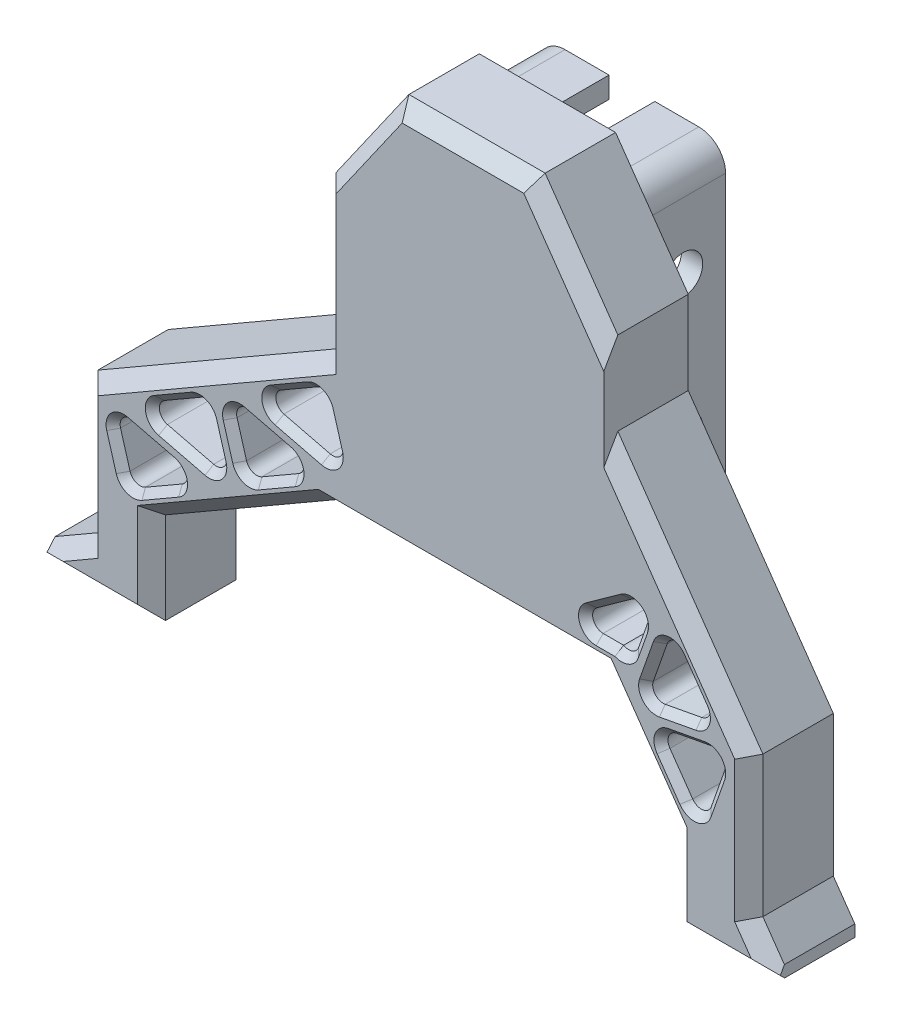
SolidWorks part; units mm, degrees
ref_plane "Front Plane" through (0, 0, 0) normal (0, 0, 1) x (1, 0, 0)
ref_plane "Top Plane" through (0, 0, 0) normal (0, 1, 0) x (1, 0, 0)
ref_plane "Right Plane" through (0, 0, 0) normal (1, 0, 0) x (0, 0, -1)
sketch "Sketch1" plane through (0, 0, 0) normal (0, 0, 1) x (1, 0, 0)
  line L0 (-3.25, 20.3) -> (-3.25, 23.3)
  line L1 (-3.05, 20.9) -> (-3.05, 23.3537) construction
  line L2 (3.25, 23.3) -> (3.25, 20.3)
  line L3 (3.05, 20.9) -> (3.05, 23.3537) construction
  line L94 (-10, -14.58) -> (-10, -19.5)
  line L95 (-9.5, -20) -> (-4.58, -20)
  line L96 (-4.58, -20) -> (-3.125, -18.545)
  line L97 (-3.125, -18.545) -> (-3.125, -18.2)
  line L98 (-3.125, -18.2) -> (-5.5, -18.2)
  line L99 (-5.5, -18.2) -> (-5.5, -16.5607)
  line L100 (-5.5, -16.5607) -> (-2.8393, -13.9)
  line L101 (-2.8393, -13.9) -> (-0.2, -13.9)
  line L102 (-0.2, -13.9) -> (0, -13.7)
  line L103 (0, -13.7) -> (0.2, -13.9)
  line L104 (0.2, -13.9) -> (2.8393, -13.9)
  line L105 (2.8393, -13.9) -> (5.5, -16.5607)
  line L106 (5.5, -16.5607) -> (5.5, -18.2)
  line L107 (5.5, -18.2) -> (3.125, -18.2)
  line L108 (3.125, -18.2) -> (3.125, -18.545)
  line L109 (3.125, -18.545) -> (4.58, -20)
  line L110 (4.58, -20) -> (9.5, -20)
  line L111 (10, -19.5) -> (10, -14.58)
  line L112 (10, -14.58) -> (8.545, -13.125)
  line L113 (8.545, -13.125) -> (8.2, -13.125)
  line L114 (8.2, -13.125) -> (8.2, -15.5)
  line L115 (8.2, -15.5) -> (6.5607, -15.5)
  line L116 (6.5607, -15.5) -> (3.9, -12.8393)
  line L117 (3.9, -12.8393) -> (3.9, -10.2)
  line L118 (3.9, -10.2) -> (3.7, -10)
  line L119 (3.7, -10) -> (3.9, -9.8)
  line L120 (3.9, -9.8) -> (3.9, -7.1607)
  line L121 (3.9, -7.1607) -> (6.5607, -4.5)
  line L122 (6.5607, -4.5) -> (8.2, -4.5)
  line L123 (8.2, -4.5) -> (8.2, -6.875)
  line L124 (8.2, -6.875) -> (8.545, -6.875)
  line L125 (8.545, -6.875) -> (10, -5.42)
  line L126 (10, -5.42) -> (10, 5.42)
  line L127 (10, 5.42) -> (8.545, 6.875)
  line L128 (8.545, 6.875) -> (8.2, 6.875)
  line L129 (8.2, 6.875) -> (8.2, 4.5)
  line L130 (8.2, 4.5) -> (6.5607, 4.5)
  line L131 (6.5607, 4.5) -> (3.9, 7.1607)
  line L132 (3.9, 7.1607) -> (3.9, 9.8)
  line L133 (3.9, 9.8) -> (3.7, 10)
  line L134 (3.7, 10) -> (3.9, 10.2)
  line L135 (3.9, 10.2) -> (3.9, 12.8393)
  line L136 (3.9, 12.8393) -> (6.5607, 15.5)
  line L137 (6.5607, 15.5) -> (8.2, 15.5)
  line L138 (8.2, 15.5) -> (8.2, 13.125)
  line L139 (8.2, 13.125) -> (8.545, 13.125)
  line L140 (8.545, 13.125) -> (10, 14.58)
  line L141 (10, 14.58) -> (10, 19.5)
  line L142 (9.5, 20) -> (4.58, 20)
  line L143 (4.58, 20) -> (3.125, 18.545)
  line L144 (3.125, 18.545) -> (3.125, 18.2)
  line L145 (3.125, 18.2) -> (5.5, 18.2)
  line L146 (5.5, 18.2) -> (5.5, 16.5607)
  line L147 (5.5, 16.5607) -> (2.8393, 13.9)
  line L148 (2.8393, 13.9) -> (0.2, 13.9)
  line L149 (0.2, 13.9) -> (0, 13.7)
  line L150 (0, 13.7) -> (-0.2, 13.9)
  line L151 (-0.2, 13.9) -> (-2.8393, 13.9)
  line L152 (-2.8393, 13.9) -> (-5.5, 16.5607)
  line L153 (-5.5, 16.5607) -> (-5.5, 18.2)
  line L154 (-5.5, 18.2) -> (-3.125, 18.2)
  line L155 (-3.125, 18.2) -> (-3.125, 18.545)
  line L156 (-3.125, 18.545) -> (-4.58, 20)
  line L157 (-4.58, 20) -> (-9.5, 20)
  line L158 (-10, 19.5) -> (-10, 14.58)
  line L159 (-10, 14.58) -> (-8.545, 13.125)
  line L160 (-8.545, 13.125) -> (-8.2, 13.125)
  line L161 (-8.2, 13.125) -> (-8.2, 15.5)
  line L162 (-8.2, 15.5) -> (-6.5607, 15.5)
  line L163 (-6.5607, 15.5) -> (-3.9, 12.8393)
  line L164 (-3.9, 12.8393) -> (-3.9, 10.2)
  line L165 (-3.9, 10.2) -> (-3.7, 10)
  line L166 (-3.7, 10) -> (-3.9, 9.8)
  line L167 (-3.9, 9.8) -> (-3.9, 7.1607)
  line L168 (-3.9, 7.1607) -> (-6.5607, 4.5)
  line L169 (-6.5607, 4.5) -> (-8.2, 4.5)
  line L170 (-8.2, 4.5) -> (-8.2, 6.875)
  line L171 (-8.2, 6.875) -> (-8.545, 6.875)
  line L172 (-8.545, 6.875) -> (-10, 5.42)
  line L173 (-10, 5.42) -> (-10, -5.42)
  line L174 (-10, -5.42) -> (-8.545, -6.875)
  line L175 (-8.545, -6.875) -> (-8.2, -6.875)
  line L176 (-8.2, -6.875) -> (-8.2, -4.5)
  line L177 (-8.2, -4.5) -> (-6.5607, -4.5)
  line L178 (-6.5607, -4.5) -> (-3.9, -7.1607)
  line L179 (-3.9, -7.1607) -> (-3.9, -9.8)
  line L180 (-3.9, -9.8) -> (-3.7, -10)
  line L181 (-3.7, -10) -> (-3.9, -10.2)
  line L182 (-3.9, -10.2) -> (-3.9, -12.8393)
  line L183 (-3.9, -12.8393) -> (-6.5607, -15.5)
  line L184 (-6.5607, -15.5) -> (-8.2, -15.5)
  line L185 (-8.2, -15.5) -> (-8.2, -13.125)
  line L186 (-8.2, -13.125) -> (-8.545, -13.125)
  line L187 (-8.545, -13.125) -> (-10, -14.58)
  line L188 (-10, -14.58) -> (-10, -19.5) construction
  line L189 (-9.5, -20) -> (-4.58, -20) construction
  line L190 (-4.58, -20) -> (-3.125, -18.545) construction
  line L191 (-3.125, -18.545) -> (-3.125, -18.2) construction
  line L192 (-3.125, -18.2) -> (-5.5, -18.2) construction
  line L193 (-5.5, -18.2) -> (-5.5, -16.5607) construction
  line L194 (-5.5, -16.5607) -> (-2.8393, -13.9) construction
  line L195 (-2.8393, -13.9) -> (-0.2, -13.9) construction
  line L196 (-0.2, -13.9) -> (0, -13.7) construction
  line L197 (0, -13.7) -> (0.2, -13.9) construction
  line L198 (0.2, -13.9) -> (2.8393, -13.9) construction
  line L199 (2.8393, -13.9) -> (5.5, -16.5607) construction
  line L200 (5.5, -16.5607) -> (5.5, -18.2) construction
  line L201 (5.5, -18.2) -> (3.125, -18.2) construction
  line L202 (3.125, -18.2) -> (3.125, -18.545) construction
  line L203 (3.125, -18.545) -> (4.58, -20) construction
  line L204 (4.58, -20) -> (9.5, -20) construction
  line L205 (10, -19.5) -> (10, -14.58) construction
  line L206 (10, -14.58) -> (8.545, -13.125) construction
  line L207 (8.545, -13.125) -> (8.2, -13.125) construction
  line L208 (8.2, -13.125) -> (8.2, -15.5) construction
  line L209 (8.2, -15.5) -> (6.5607, -15.5) construction
  line L210 (6.5607, -15.5) -> (3.9, -12.8393) construction
  line L211 (3.9, -12.8393) -> (3.9, -10.2) construction
  line L212 (3.9, -10.2) -> (3.7, -10) construction
  line L213 (3.7, -10) -> (3.9, -9.8) construction
  line L214 (3.9, -9.8) -> (3.9, -7.1607) construction
  line L215 (3.9, -7.1607) -> (6.5607, -4.5) construction
  line L216 (6.5607, -4.5) -> (8.2, -4.5) construction
  line L217 (8.2, -4.5) -> (8.2, -6.875) construction
  line L218 (8.2, -6.875) -> (8.545, -6.875) construction
  line L219 (8.545, -6.875) -> (10, -5.42) construction
  line L220 (10, -5.42) -> (10, 5.42) construction
  line L221 (10, 5.42) -> (8.545, 6.875) construction
  line L222 (8.545, 6.875) -> (8.2, 6.875) construction
  line L223 (8.2, 6.875) -> (8.2, 4.5) construction
  line L224 (8.2, 4.5) -> (6.5607, 4.5) construction
  line L225 (6.5607, 4.5) -> (3.9, 7.1607) construction
  line L226 (3.9, 7.1607) -> (3.9, 9.8) construction
  line L227 (3.9, 9.8) -> (3.7, 10) construction
  line L228 (3.7, 10) -> (3.9, 10.2) construction
  line L229 (3.9, 10.2) -> (3.9, 12.8393) construction
  line L230 (3.9, 12.8393) -> (6.5607, 15.5) construction
  line L231 (6.5607, 15.5) -> (8.2, 15.5) construction
  line L232 (8.2, 15.5) -> (8.2, 13.125) construction
  line L233 (8.2, 13.125) -> (8.545, 13.125) construction
  line L234 (8.545, 13.125) -> (10, 14.58) construction
  line L235 (10, 14.58) -> (10, 19.5) construction
  line L236 (9.5, 20) -> (4.58, 20) construction
  line L237 (4.58, 20) -> (3.125, 18.545) construction
  line L238 (3.125, 18.545) -> (3.125, 18.2) construction
  line L239 (3.125, 18.2) -> (5.5, 18.2) construction
  line L240 (5.5, 18.2) -> (5.5, 16.5607) construction
  line L241 (5.5, 16.5607) -> (2.8393, 13.9) construction
  line L242 (2.8393, 13.9) -> (0.2, 13.9) construction
  line L243 (0.2, 13.9) -> (0, 13.7) construction
  line L244 (0, 13.7) -> (-0.2, 13.9) construction
  line L245 (-0.2, 13.9) -> (-2.8393, 13.9) construction
  line L246 (-2.8393, 13.9) -> (-5.5, 16.5607) construction
  line L247 (-5.5, 16.5607) -> (-5.5, 18.2) construction
  line L248 (-5.5, 18.2) -> (-3.125, 18.2) construction
  line L249 (-3.125, 18.2) -> (-3.125, 18.545) construction
  line L250 (-3.125, 18.545) -> (-4.58, 20) construction
  line L251 (-4.58, 20) -> (-9.5, 20) construction
  line L252 (-10, 19.5) -> (-10, 14.58) construction
  line L253 (-10, 14.58) -> (-8.545, 13.125) construction
  line L254 (-8.545, 13.125) -> (-8.2, 13.125) construction
  line L255 (-8.2, 13.125) -> (-8.2, 15.5) construction
  line L256 (-8.2, 15.5) -> (-6.5607, 15.5) construction
  line L257 (-6.5607, 15.5) -> (-3.9, 12.8393) construction
  line L258 (-3.9, 12.8393) -> (-3.9, 10.2) construction
  line L259 (-3.9, 10.2) -> (-3.7, 10) construction
  line L260 (-3.7, 10) -> (-3.9, 9.8) construction
  line L261 (-3.9, 9.8) -> (-3.9, 7.1607) construction
  line L262 (-3.9, 7.1607) -> (-6.5607, 4.5) construction
  line L263 (-6.5607, 4.5) -> (-8.2, 4.5) construction
  line L264 (-8.2, 4.5) -> (-8.2, 6.875) construction
  line L265 (-8.2, 6.875) -> (-8.545, 6.875) construction
  line L266 (-8.545, 6.875) -> (-10, 5.42) construction
  line L267 (-10, 5.42) -> (-10, -5.42) construction
  line L268 (-10, -5.42) -> (-8.545, -6.875) construction
  line L269 (-8.545, -6.875) -> (-8.2, -6.875) construction
  line L270 (-8.2, -6.875) -> (-8.2, -4.5) construction
  line L271 (-8.2, -4.5) -> (-6.5607, -4.5) construction
  line L272 (-6.5607, -4.5) -> (-3.9, -7.1607) construction
  line L273 (-3.9, -7.1607) -> (-3.9, -9.8) construction
  line L274 (-3.9, -9.8) -> (-3.7, -10) construction
  line L275 (-3.7, -10) -> (-3.9, -10.2) construction
  line L276 (-3.9, -10.2) -> (-3.9, -12.8393) construction
  line L277 (-3.9, -12.8393) -> (-6.5607, -15.5) construction
  line L278 (-6.5607, -15.5) -> (-8.2, -15.5) construction
  line L279 (-8.2, -15.5) -> (-8.2, -13.125) construction
  line L280 (-8.2, -13.125) -> (-8.545, -13.125) construction
  line L281 (-8.545, -13.125) -> (-10, -14.58) construction
  line L282 (-10.3, 14.4557) -> (-10.3, 5.5443)
  line L283 (10.3, 14.4557) -> (10.3, 5.5443)
  line L284 (10.3, -5.5443) -> (10.3, -14.4557)
  line L285 (-10.3, -5.5443) -> (-10.3, -14.4557)
  line L286 (-4.4557, -20.3) -> (4.4557, -20.3)
  line L287 (-4.4557, 20.3) -> (4.4557, 20.3)
  line L288 (-4.4557, 23.3) -> (-9.5, 23.3)
  line L289 (-13.3, 19.5) -> (-13.3, 14.4557)
  line L290 (-13.3, 14.4557) -> (-13.3, 5.5443)
  line L291 (-13.3, 5.5443) -> (-13.3, -5.5443)
  line L292 (-13.3, -5.5443) -> (-13.3, -14.4557)
  line L293 (-13.3, -14.4557) -> (-13.3, -19.5)
  line L294 (-9.5, -23.3) -> (-4.4557, -23.3)
  line L295 (-4.4557, -23.3) -> (4.4557, -23.3)
  line L296 (4.4557, -23.3) -> (9.5, -23.3)
  line L297 (13.3, -19.5) -> (13.3, -14.4557)
  line L298 (13.3, -5.5443) -> (13.3, -14.4557)
  line L299 (13.3, -5.5443) -> (13.3, 5.5443)
  line L300 (13.3, 14.4557) -> (13.3, 5.5443)
  line L301 (13.3, 14.4557) -> (13.3, 19.5)
  line L302 (9.5, 23.3) -> (4.4557, 23.3)
  line L303 (-4.4557, 23.3) -> (4.4557, 23.3)
  line L376 (-10.3, -14.4557) -> (-10.3, -19.5)
  line L377 (-9.5, -20.3) -> (-4.4557, -20.3)
  line L378 (-4.4557, -20.3) -> (-2.825, -18.6693)
  line L379 (-2.825, -18.6693) -> (-2.825, -17.9)
  line L380 (-2.825, -17.9) -> (-5.2, -17.9)
  line L381 (-5.2, -17.9) -> (-5.2, -16.6849)
  line L382 (-5.2, -16.6849) -> (-2.7151, -14.2)
  line L383 (-2.7151, -14.2) -> (-0.0757, -14.2)
  line L384 (2.7151, -14.2) -> (5.2, -16.6849)
  line L385 (5.2, -16.6849) -> (5.2, -17.9)
  line L386 (5.2, -17.9) -> (2.825, -17.9)
  line L387 (2.825, -17.9) -> (2.825, -18.6693)
  line L388 (2.825, -18.6693) -> (4.4557, -20.3)
  line L389 (4.4557, -20.3) -> (9.5, -20.3)
  line L390 (10.3, -19.5) -> (10.3, -14.4557)
  line L391 (10.3, -14.4557) -> (8.6693, -12.825)
  line L392 (8.6693, -12.825) -> (7.9, -12.825)
  line L393 (7.9, -12.825) -> (7.9, -15.2)
  line L394 (7.9, -15.2) -> (6.6849, -15.2)
  line L395 (6.6849, -15.2) -> (4.2, -12.7151)
  line L396 (4.2, -12.7151) -> (4.2, -10.0757)
  line L397 (4.2, -7.2849) -> (6.6849, -4.8)
  line L398 (6.6849, -4.8) -> (7.9, -4.8)
  line L399 (7.9, -4.8) -> (7.9, -7.175)
  line L400 (7.9, -7.175) -> (8.6693, -7.175)
  line L401 (8.6693, -7.175) -> (10.3, -5.5443)
  line L402 (10.3, -5.5443) -> (10.3, 5.5443)
  line L403 (10.3, 5.5443) -> (8.6693, 7.175)
  line L404 (8.6693, 7.175) -> (7.9, 7.175)
  line L405 (7.9, 7.175) -> (7.9, 4.8)
  line L406 (7.9, 4.8) -> (6.6849, 4.8)
  line L407 (6.6849, 4.8) -> (4.2, 7.2849)
  line L408 (4.2, 7.2849) -> (4.2, 9.9243)
  line L409 (4.2, 12.7151) -> (6.6849, 15.2)
  line L410 (6.6849, 15.2) -> (7.9, 15.2)
  line L411 (7.9, 15.2) -> (7.9, 12.825)
  line L412 (7.9, 12.825) -> (8.6693, 12.825)
  line L413 (8.6693, 12.825) -> (10.3, 14.4557)
  line L414 (10.3, 14.4557) -> (10.3, 19.5)
  line L415 (9.5, 20.3) -> (4.4557, 20.3)
  line L416 (4.4557, 20.3) -> (2.825, 18.6693)
  line L417 (2.825, 18.6693) -> (2.825, 17.9)
  line L418 (2.825, 17.9) -> (5.2, 17.9)
  line L419 (5.2, 17.9) -> (5.2, 16.6849)
  line L420 (5.2, 16.6849) -> (2.7151, 14.2)
  line L421 (2.7151, 14.2) -> (0.0757, 14.2)
  line L422 (-2.7151, 14.2) -> (-5.2, 16.6849)
  line L423 (-5.2, 16.6849) -> (-5.2, 17.9)
  line L424 (-5.2, 17.9) -> (-2.825, 17.9)
  line L425 (-2.825, 17.9) -> (-2.825, 18.6693)
  line L426 (-2.825, 18.6693) -> (-4.4557, 20.3)
  line L427 (-4.4557, 20.3) -> (-9.5, 20.3)
  line L428 (-10.3, 19.5) -> (-10.3, 14.4557)
  line L429 (-10.3, 14.4557) -> (-8.6693, 12.825)
  line L430 (-8.6693, 12.825) -> (-7.9, 12.825)
  line L431 (-7.9, 12.825) -> (-7.9, 15.2)
  line L432 (-7.9, 15.2) -> (-6.6849, 15.2)
  line L433 (-6.6849, 15.2) -> (-4.2, 12.7151)
  line L434 (-4.2, 12.7151) -> (-4.2, 10.0757)
  line L435 (-4.2, 7.2849) -> (-6.6849, 4.8)
  line L436 (-6.6849, 4.8) -> (-7.9, 4.8)
  line L437 (-7.9, 4.8) -> (-7.9, 7.175)
  line L438 (-7.9, 7.175) -> (-8.6693, 7.175)
  line L439 (-8.6693, 7.175) -> (-10.3, 5.5443)
  line L440 (-10.3, 5.5443) -> (-10.3, -5.5443)
  line L441 (-10.3, -5.5443) -> (-8.6693, -7.175)
  line L442 (-8.6693, -7.175) -> (-7.9, -7.175)
  line L443 (-7.9, -7.175) -> (-7.9, -4.8)
  line L444 (-7.9, -4.8) -> (-6.6849, -4.8)
  line L445 (-6.6849, -4.8) -> (-4.2, -7.2849)
  line L446 (-4.2, -7.2849) -> (-4.2, -9.9243)
  line L447 (-4.2, -12.7151) -> (-6.6849, -15.2)
  line L448 (-6.6849, -15.2) -> (-7.9, -15.2)
  line L449 (-7.9, -15.2) -> (-7.9, -12.825)
  line L450 (-7.9, -12.825) -> (-8.6693, -12.825)
  line L451 (-8.6693, -12.825) -> (-10.3, -14.4557)
  line L452 (-10.3, -14.4557) -> (-10.3, -19.5)
  line L453 (-9.5, -20.3) -> (-4.4557, -20.3)
  line L454 (-4.4557, -20.3) -> (-2.825, -18.6693)
  line L455 (-2.825, -18.6693) -> (-2.825, -17.9)
  line L456 (-2.825, -17.9) -> (-5.2, -17.9)
  line L457 (-5.2, -17.9) -> (-5.2, -16.6849)
  line L458 (-5.2, -16.6849) -> (-2.7151, -14.2)
  line L459 (-2.7151, -14.2) -> (-0.0757, -14.2)
  line L460 (2.7151, -14.2) -> (5.2, -16.6849)
  line L461 (5.2, -16.6849) -> (5.2, -17.9)
  line L462 (5.2, -17.9) -> (2.825, -17.9)
  line L463 (2.825, -17.9) -> (2.825, -18.6693)
  line L464 (2.825, -18.6693) -> (4.4557, -20.3)
  line L465 (4.4557, -20.3) -> (9.5, -20.3)
  line L466 (10.3, -19.5) -> (10.3, -14.4557)
  line L467 (10.3, -14.4557) -> (8.6693, -12.825)
  line L468 (8.6693, -12.825) -> (7.9, -12.825)
  line L469 (7.9, -12.825) -> (7.9, -15.2)
  line L470 (7.9, -15.2) -> (6.6849, -15.2)
  line L471 (6.6849, -15.2) -> (4.2, -12.7151)
  line L472 (4.2, -12.7151) -> (4.2, -10.0757)
  line L473 (4.2, -7.2849) -> (6.6849, -4.8)
  line L474 (6.6849, -4.8) -> (7.9, -4.8)
  line L475 (7.9, -4.8) -> (7.9, -7.175)
  line L476 (7.9, -7.175) -> (8.6693, -7.175)
  line L477 (8.6693, -7.175) -> (10.3, -5.5443)
  line L478 (10.3, -5.5443) -> (10.3, 5.5443)
  line L479 (10.3, 5.5443) -> (8.6693, 7.175)
  line L480 (8.6693, 7.175) -> (7.9, 7.175)
  line L481 (7.9, 7.175) -> (7.9, 4.8)
  line L482 (7.9, 4.8) -> (6.6849, 4.8)
  line L483 (6.6849, 4.8) -> (4.2, 7.2849)
  line L484 (4.2, 7.2849) -> (4.2, 9.9243)
  line L485 (4.2, 12.7151) -> (6.6849, 15.2)
  line L486 (6.6849, 15.2) -> (7.9, 15.2)
  line L487 (7.9, 15.2) -> (7.9, 12.825)
  line L488 (7.9, 12.825) -> (8.6693, 12.825)
  line L489 (8.6693, 12.825) -> (10.3, 14.4557)
  line L490 (10.3, 14.4557) -> (10.3, 19.5)
  line L491 (9.5, 20.3) -> (4.4557, 20.3)
  line L492 (4.4557, 20.3) -> (2.825, 18.6693)
  line L493 (2.825, 18.6693) -> (2.825, 17.9)
  line L494 (2.825, 17.9) -> (5.2, 17.9)
  line L495 (5.2, 17.9) -> (5.2, 16.6849)
  line L496 (5.2, 16.6849) -> (2.7151, 14.2)
  line L497 (2.7151, 14.2) -> (0.0757, 14.2)
  line L498 (-2.7151, 14.2) -> (-5.2, 16.6849)
  line L499 (-5.2, 16.6849) -> (-5.2, 17.9)
  line L500 (-5.2, 17.9) -> (-2.825, 17.9)
  line L501 (-2.825, 17.9) -> (-2.825, 18.6693)
  line L502 (-2.825, 18.6693) -> (-4.4557, 20.3)
  line L503 (-4.4557, 20.3) -> (-9.5, 20.3)
  line L504 (-10.3, 19.5) -> (-10.3, 14.4557)
  line L505 (-10.3, 14.4557) -> (-8.6693, 12.825)
  line L506 (-8.6693, 12.825) -> (-7.9, 12.825)
  line L507 (-7.9, 12.825) -> (-7.9, 15.2)
  line L508 (-7.9, 15.2) -> (-6.6849, 15.2)
  line L509 (-6.6849, 15.2) -> (-4.2, 12.7151)
  line L510 (-4.2, 12.7151) -> (-4.2, 10.0757)
  line L511 (-4.2, 7.2849) -> (-6.6849, 4.8)
  line L512 (-6.6849, 4.8) -> (-7.9, 4.8)
  line L513 (-7.9, 4.8) -> (-7.9, 7.175)
  line L514 (-7.9, 7.175) -> (-8.6693, 7.175)
  line L515 (-8.6693, 7.175) -> (-10.3, 5.5443)
  line L516 (-10.3, 5.5443) -> (-10.3, -5.5443)
  line L517 (-10.3, -5.5443) -> (-8.6693, -7.175)
  line L518 (-8.6693, -7.175) -> (-7.9, -7.175)
  line L519 (-7.9, -7.175) -> (-7.9, -4.8)
  line L520 (-7.9, -4.8) -> (-6.6849, -4.8)
  line L521 (-6.6849, -4.8) -> (-4.2, -7.2849)
  line L522 (-4.2, -7.2849) -> (-4.2, -9.9243)
  line L523 (-4.2, -12.7151) -> (-6.6849, -15.2)
  line L524 (-6.6849, -15.2) -> (-7.9, -15.2)
  line L525 (-7.9, -15.2) -> (-7.9, -12.825)
  line L526 (-7.9, -12.825) -> (-8.6693, -12.825)
  line L527 (-8.6693, -12.825) -> (-10.3, -14.4557)
  line L528 (-0.0757, -14.2) -> (0, -14.1243)
  line L529 (-0.0757, -14.2) -> (0, -14.1243)
  line L530 (0, -14.1243) -> (0.0757, -14.2)
  line L531 (0, -14.1243) -> (0.0757, -14.2)
  line L532 (0.0757, -14.2) -> (2.7151, -14.2)
  line L533 (0.0757, -14.2) -> (2.7151, -14.2)
  line L534 (4.2, -10.0757) -> (4.1243, -10)
  line L535 (4.2, -10.0757) -> (4.1243, -10)
  line L536 (4.1243, -10) -> (4.2, -9.9243)
  line L537 (4.1243, -10) -> (4.2, -9.9243)
  line L538 (4.2, -9.9243) -> (4.2, -7.2849)
  line L539 (4.2, -9.9243) -> (4.2, -7.2849)
  line L540 (4.2, 9.9243) -> (4.1243, 10)
  line L541 (4.2, 9.9243) -> (4.1243, 10)
  line L542 (4.1243, 10) -> (4.2, 10.0757)
  line L543 (4.1243, 10) -> (4.2, 10.0757)
  line L544 (4.2, 10.0757) -> (4.2, 12.7151)
  line L545 (4.2, 10.0757) -> (4.2, 12.7151)
  line L546 (0.0757, 14.2) -> (0, 14.1243)
  line L547 (0.0757, 14.2) -> (0, 14.1243)
  line L548 (0, 14.1243) -> (-0.0757, 14.2)
  line L549 (0, 14.1243) -> (-0.0757, 14.2)
  line L550 (-0.0757, 14.2) -> (-2.7151, 14.2)
  line L551 (-0.0757, 14.2) -> (-2.7151, 14.2)
  line L552 (-4.2, 10.0757) -> (-4.1243, 10)
  line L553 (-4.2, 10.0757) -> (-4.1243, 10)
  line L554 (-4.1243, 10) -> (-4.2, 9.9243)
  line L555 (-4.1243, 10) -> (-4.2, 9.9243)
  line L556 (-4.2, 9.9243) -> (-4.2, 7.2849)
  line L557 (-4.2, 9.9243) -> (-4.2, 7.2849)
  line L558 (-4.2, -9.9243) -> (-4.1243, -10)
  line L559 (-4.2, -9.9243) -> (-4.1243, -10)
  line L560 (-4.1243, -10) -> (-4.2, -10.0757)
  line L561 (-4.1243, -10) -> (-4.2, -10.0757)
  line L562 (-4.2, -10.0757) -> (-4.2, -12.7151)
  line L563 (-4.2, -10.0757) -> (-4.2, -12.7151)
  arc A4 (-10, -19.5) -> (-9.5, -20) centre (-9.5, -19.5) ccw
  arc A5 (9.5, -20) -> (10, -19.5) centre (9.5, -19.5) ccw
  arc A6 (10, 19.5) -> (9.5, 20) centre (9.5, 19.5) ccw
  arc A7 (-9.5, 20) -> (-10, 19.5) centre (-9.5, 19.5) ccw
  arc A8 (-10, -19.5) -> (-9.5, -20) centre (-9.5, -19.5) ccw construction
  arc A9 (9.5, -20) -> (10, -19.5) centre (9.5, -19.5) ccw construction
  arc A10 (10, 19.5) -> (9.5, 20) centre (9.5, 19.5) ccw construction
  arc A11 (-9.5, 20) -> (-10, 19.5) centre (-9.5, 19.5) ccw construction
  arc A12 (-9.5, 23.3) -> (-13.3, 19.5) centre (-9.5, 19.5) ccw
  arc A13 (-13.3, -19.5) -> (-9.5, -23.3) centre (-9.5, -19.5) ccw
  arc A14 (9.5, -23.3) -> (13.3, -19.5) centre (9.5, -19.5) ccw
  arc A15 (13.3, 19.5) -> (9.5, 23.3) centre (9.5, 19.5) ccw
  arc A16 (-10.3, -19.5) -> (-9.5, -20.3) centre (-9.5, -19.5) ccw
  arc A17 (9.5, -20.3) -> (10.3, -19.5) centre (9.5, -19.5) ccw
  arc A18 (10.3, 19.5) -> (9.5, 20.3) centre (9.5, 19.5) ccw
  arc A19 (-9.5, 20.3) -> (-10.3, 19.5) centre (-9.5, 19.5) ccw
  arc A20 (-10.3, -19.5) -> (-9.5, -20.3) centre (-9.5, -19.5) ccw
  arc A21 (9.5, -20.3) -> (10.3, -19.5) centre (9.5, -19.5) ccw
  arc A22 (10.3, 19.5) -> (9.5, 20.3) centre (9.5, 19.5) ccw
  arc A23 (-9.5, 20.3) -> (-10.3, 19.5) centre (-9.5, 19.5) ccw
  dimension "D4" = 0.2
  dimension "D5" = 0.2
  dimension "D1" = 0
  dimension "D2" = 0.3
  dimension "D3" = 3
extrude "Boss-Extrude1" add sketch "Sketch1" against normal blind 12 contours L301 A15 L302 L303 L288 A12 L289 L290 L291 L292 L293 A13 L294 L295 L296 A14 L297 L298 L299 L300 A23 L503 L287 L491 A22 L490 L283 L478 L284 L466 A21 L465 L286 L453 A20 L452 L285 L516 L282 L504 region at (-3.8529, 20.8366, 0)
sketch "Sketch2" plane through (0, 0, 0) normal (0, 0, 1) x (1, 0, 0)
  line L0 (20, 13.9553) -> (9.6756, 28.7)
  line L1 (-20, -26.3) -> (20, -26.3)
  line L2 (-20, -26.3) -> (-20, 28.7)
  line L3 (-20, 28.7) -> (20, 28.7)
  line L4 (20, -26.3) -> (20, 28.7)
  line L5 (-20, -26.3) -> (20, 28.7) construction
  line L6 (-20, 28.7) -> (20, -26.3) construction
  line L7 (-20, 13.9553) -> (-9.6756, 28.7)
  line L8 (-9.5, -23.3) -> (9.5, -23.3) construction
  line L9 (20, 2.1222) -> (40.6017, -27.3)
  line L10 (40.6017, -27.3) -> (40.6017, -47.3)
  line L11 (40.6017, -47.3) -> (44.8029, -53.3)
  line L12 (44.8029, -53.3) -> (29.8029, -53.3)
  line L13 (29.8029, -53.3) -> (29.8029, -40.3)
  line L14 (29.8029, -40.3) -> (20, -26.3)
  line L15 (-20, -7.753) -> (-53.8564, -27.3)
  line L16 (-53.8564, -27.3) -> (-53.8564, -47.3)
  line L17 (-53.8564, -47.3) -> (-64.2487, -53.3)
  line L18 (-64.2487, -53.3) -> (-44.2487, -53.3)
  line L19 (-44.2487, -53.3) -> (-44.2487, -40.3)
  line L20 (-44.2487, -40.3) -> (-20, -26.3)
  line L21 (-9.5, 20.3) -> (-3.25, 20.3)
  line L22 (-3.25, 20.3) -> (-3.25, 23.3)
  line L23 (-3.25, 23.3) -> (-9.5, 23.3)
  line L24 (-13.3, 19.5) -> (-13.3, -19.5)
  line L25 (-9.5, -23.3) -> (9.5, -23.3)
  line L26 (13.3, -19.5) -> (13.3, 19.5)
  line L27 (9.5, 23.3) -> (3.25, 23.3)
  line L28 (3.25, 23.3) -> (3.25, 20.3)
  line L29 (3.25, 20.3) -> (9.5, 20.3)
  line L30 (10.3, 19.5) -> (10.3, -19.5)
  line L31 (9.5, -20.3) -> (-9.5, -20.3)
  line L32 (-10.3, -19.5) -> (-10.3, 19.5)
  line L33 (-9.5, 20.3) -> (-3.25, 20.3)
  line L34 (-3.25, 20.3) -> (-3.25, 23.3)
  line L35 (-3.25, 23.3) -> (-9.5, 23.3)
  line L36 (-13.3, 19.5) -> (-13.3, -19.5)
  line L37 (-9.5, -23.3) -> (9.5, -23.3)
  line L38 (13.3, -19.5) -> (13.3, 19.5)
  line L39 (9.5, 23.3) -> (3.25, 23.3)
  line L40 (3.25, 23.3) -> (3.25, 20.3)
  line L41 (3.25, 20.3) -> (9.5, 20.3)
  line L42 (10.3, 19.5) -> (10.3, -19.5)
  line L43 (9.5, -20.3) -> (-9.5, -20.3)
  line L44 (-10.3, -19.5) -> (-10.3, 19.5)
  arc A8 (-9.5, 20.3) -> (-10.3, 19.5) centre (-9.5, 19.5) ccw
  arc A9 (-9.5, 23.3) -> (-13.3, 19.5) centre (-9.5, 19.5) ccw
  arc A10 (-13.3, -19.5) -> (-9.5, -23.3) centre (-9.5, -19.5) ccw
  arc A11 (9.5, -23.3) -> (13.3, -19.5) centre (9.5, -19.5) ccw
  arc A12 (13.3, 19.5) -> (9.5, 23.3) centre (9.5, 19.5) ccw
  arc A13 (10.3, 19.5) -> (9.5, 20.3) centre (9.5, 19.5) ccw
  arc A14 (9.5, -20.3) -> (10.3, -19.5) centre (9.5, -19.5) ccw
  arc A15 (-10.3, -19.5) -> (-9.5, -20.3) centre (-9.5, -19.5) ccw
  arc A16 (-9.5, 20.3) -> (-10.3, 19.5) centre (-9.5, 19.5) ccw
  arc A17 (-9.5, 23.3) -> (-13.3, 19.5) centre (-9.5, 19.5) ccw
  arc A18 (-13.3, -19.5) -> (-9.5, -23.3) centre (-9.5, -19.5) ccw
  arc A19 (9.5, -23.3) -> (13.3, -19.5) centre (9.5, -19.5) ccw
  arc A20 (13.3, 19.5) -> (9.5, 23.3) centre (9.5, 19.5) ccw
  arc A21 (10.3, 19.5) -> (9.5, 20.3) centre (9.5, 19.5) ccw
  arc A22 (9.5, -20.3) -> (10.3, -19.5) centre (9.5, -19.5) ccw
  arc A23 (-10.3, -19.5) -> (-9.5, -20.3) centre (-9.5, -19.5) ccw
  point P0 (0, 0)
  point P5 (0, -26.3)
  point P21 (0, -23.3)
  arc M39 (-10.3, 19.5) -> (-9.5, 20.3) centre (-9.5, 19.5) cw
  line M40 (-9.5, 20.3) -> (-3.25, 20.3)
  line M41 (-3.25, 20.3) -> (-3.25, 23.3)
  line M42 (-3.25, 23.3) -> (-9.5, 23.3)
  arc M43 (-9.5, 23.3) -> (-13.3, 19.5) centre (-9.5, 19.5) ccw
  line M44 (-13.3, 19.5) -> (-13.3, -19.5)
  arc M45 (-13.3, -19.5) -> (-9.5, -23.3) centre (-9.5, -19.5) ccw
  line M46 (-9.5, -23.3) -> (9.5, -23.3)
  arc M47 (9.5, -23.3) -> (13.3, -19.5) centre (9.5, -19.5) ccw
  line M48 (13.3, -19.5) -> (13.3, 19.5)
  arc M49 (13.3, 19.5) -> (9.5, 23.3) centre (9.5, 19.5) ccw
  line M50 (9.5, 23.3) -> (3.25, 23.3)
  line M51 (3.25, 23.3) -> (3.25, 20.3)
  line M52 (3.25, 20.3) -> (9.5, 20.3)
  arc M53 (9.5, 20.3) -> (10.3, 19.5) centre (9.5, 19.5) cw
  line M54 (10.3, 19.5) -> (10.3, -19.5)
  arc M55 (10.3, -19.5) -> (9.5, -20.3) centre (9.5, -19.5) cw
  line M56 (9.5, -20.3) -> (-9.5, -20.3)
  arc M57 (-9.5, -20.3) -> (-10.3, -19.5) centre (-9.5, -19.5) cw
  line M58 (-10.3, -19.5) -> (-10.3, 19.5)
  dimension "D1" = 55
  dimension "D2" = 40
  dimension "D3" = 3
  dimension "D4" = 0
  dimension "D5" = 35
  dimension "D6" = 18
  dimension "D7" = 35
  dimension "D8" = 18
  dimension "D9" = 15
  dimension "D10" = 56
  dimension "D11" = 20
  dimension "D12" = 6
  dimension "D13" = 13
  dimension "D14" = 20
  dimension "15" = 35
  dimension "D15" = 13
  dimension "D16" = 56
  dimension "D17" = 20
  dimension "D18" = 6
  dimension "D19" = 60
extrude "Boss-Extrude2" add sketch "Sketch2" along normal blind 12 separate body contours L7 L2 L1 L4 L0 L3 M39 M58 M57 M56 M55 M54 M53 M52 M51 M50 M49 M48 M47 M46 M45 M44 M43 M42 M41 M40 | L19 L20 L2 L15 L16 L17 L18 | L14 L13 L12 L11 L10 L9 L4 | M58 M39 M40 M41 M42 M43 M44 M45 M46 M47 M48 M49 M50 M51 M52 M53 M54 M55 M56 M57 region at (0, -0.3316, 0) region at (30.7244, -29.1872, 0) region at (-39.2842, -30.5668, 0) region at (-10.4451, 20.4451, 0)
chamfer "Chamfer1" distance 5 angle 60 1 edges at (-64.2487, -53.3, 6) first distance on face at (-59.0526, -50.3, 6)
chamfer "Chamfer2" distance 2 angle 34 1 edges at (44.8029, -53.3, 6) first distance on face at (42.7023, -50.3, 6)
chamfer "Chamfer3" distance 2 angle 45 17 edges at (-52.0836, -53.3, 12) (-44.2487, -46.8, 12) (-32.1244, -33.3, 12) (0, -26.3, 12) (24.9015, -33.3, 12) (29.8029, -46.8, 12) (36.7436, -53.3, 12) (42.1287, -49.4808, 12) (40.6017, -37.3, 12) (30.3008, -12.5889, 12) (-56.8875, -49.05, 12) (-53.8564, -37.3, 12) (-36.9282, -17.5265, 12) (14.8378, 21.3276, 12) (-20, 3.1011, 12) (-14.8378, 21.3276, 12) (0, 28.7, 12)
sketch "Sketch3" plane through (0, 0, 12) normal (0, 0, 1) x (1, 0, 0)
  line L0 (-16.5, -9.7737) -> (-50.3564, -29.3207)
  line L1 (-50.3564, -29.3207) -> (-50.3564, -49.3207)
  line L2 (-50.3564, -49.3207) -> (-51.1865, -49.8)
  line L3 (-51.1865, -49.8) -> (-47.7487, -49.8)
  line L4 (-47.7487, -49.8) -> (-47.7487, -38.2793)
  line L5 (-47.7487, -38.2793) -> (-20.9378, -22.8)
  line L6 (-20.9378, -22.8) -> (21.822, -22.8)
  line L7 (21.822, -22.8) -> (33.3029, -39.1965)
  line L8 (33.3029, -39.1965) -> (33.3029, -49.8)
  line L9 (33.3029, -49.8) -> (38.0795, -49.8)
  line L10 (38.0795, -49.8) -> (37.1017, -48.4035)
  line L11 (37.1017, -48.4035) -> (37.1017, -28.4035)
  line L12 (37.1017, -28.4035) -> (18.5, -1.8376)
  line L13 (18.5, -1.8376) -> (18.5, 9.9954)
  line L14 (18.5, 9.9954) -> (7.8536, 25.2)
  line L15 (7.8536, 25.2) -> (-7.8536, 25.2)
  line L16 (-7.8536, 25.2) -> (-16.5, 12.8517)
  line L17 (-16.5, 12.8517) -> (-16.5, -9.7737)
  line L18 (38.6017, -27.9306) -> (20, -1.3647)
  line L19 (20, -1.3647) -> (20, 10.4684)
  line L20 (20, 10.4684) -> (8.6345, 26.7)
  line L21 (8.6345, 26.7) -> (-8.6345, 26.7)
  line L22 (-8.6345, 26.7) -> (-18, 13.3247)
  line L23 (-18, 13.3247) -> (-18, -8.9077)
  line L24 (-18, -8.9077) -> (-51.8564, -28.4547)
  line L25 (-51.8564, -28.4547) -> (-51.8564, -48.4547)
  line L26 (-51.8564, -48.4547) -> (-56.7846, -51.3)
  line L27 (-56.7846, -51.3) -> (-46.2487, -51.3)
  line L28 (-46.2487, -51.3) -> (-46.2487, -39.1453)
  line L29 (-46.2487, -39.1453) -> (-20.5359, -24.3)
  line L30 (-20.5359, -24.3) -> (21.0411, -24.3)
  line L31 (21.0411, -24.3) -> (31.8029, -39.6694)
  line L32 (31.8029, -39.6694) -> (31.8029, -51.3)
  line L33 (31.8029, -51.3) -> (40.9609, -51.3)
  line L34 (40.9609, -51.3) -> (38.6017, -47.9306)
  line L35 (38.6017, -47.9306) -> (38.6017, -27.9306)
  line L36 (38.6017, -27.9306) -> (20, -1.3647)
  line L37 (20, -1.3647) -> (20, 10.4684)
  line L38 (20, 10.4684) -> (8.6345, 26.7)
  line L39 (8.6345, 26.7) -> (-8.6345, 26.7)
  line L40 (-8.6345, 26.7) -> (-18, 13.3247)
  line L41 (-18, 13.3247) -> (-18, -8.9077)
  line L42 (-18, -8.9077) -> (-51.8564, -28.4547)
  line L43 (-51.8564, -28.4547) -> (-51.8564, -48.4547)
  line L44 (-51.8564, -48.4547) -> (-56.7846, -51.3)
  line L45 (-56.7846, -51.3) -> (-46.2487, -51.3)
  line L46 (-46.2487, -51.3) -> (-46.2487, -39.1453)
  line L47 (-46.2487, -39.1453) -> (-20.5359, -24.3)
  line L48 (-20.5359, -24.3) -> (21.0411, -24.3)
  line L49 (21.0411, -24.3) -> (31.8029, -39.6694)
  line L50 (31.8029, -39.6694) -> (31.8029, -51.3)
  line L51 (31.8029, -51.3) -> (40.9609, -51.3)
  line L52 (40.9609, -51.3) -> (38.6017, -47.9306)
  line L53 (38.6017, -47.9306) -> (38.6017, -27.9306)
  line L54 (-50.3564, -29.3207) -> (-47.7487, -38.2793)
  line L55 (-50.3564, -29.3207) -> (-37.633, -32.439)
  line L56 (-46.6007, -27.1524) -> (-33.8773, -30.2706)
  line L57 (-33.8773, -30.2706) -> (-36.485, -21.3121)
  line L58 (-33.81, -19.7677) -> (-31.2023, -28.7262)
  line L59 (-33.81, -19.7677) -> (-21.0866, -22.8859)
  line L60 (-30.0544, -17.5993) -> (-8.8339, -22.8)
  line L61 (-19.9392, -11.7593) -> (-17.3316, -20.7174)
  line L62 (33.3029, -39.1965) -> (37.1017, -28.4035)
  line L63 (37.1017, -28.4035) -> (27.0624, -30.2841)
  line L64 (25.173, -27.5858) -> (35.2123, -25.7053)
  line L65 (25.173, -27.5858) -> (28.9718, -16.7929)
  line L66 (23.0565, -24.5631) -> (26.8553, -13.7702)
  line L67 (26.8553, -13.7702) -> (14.2471, -22.8)
  dimension "D3" = 3
  dimension "60" = 60
  dimension "D4" = 60
  dimension "D5" = 3
  dimension "D6" = 60
  dimension "D7" = 3
  dimension "D8" = 60
  dimension "D9" = 11.68
  dimension "D10" = 60
  dimension "D11" = 3
  dimension "D12" = 60
  dimension "D13" = 3
  dimension "D14" = 35
  dimension "D1" = 0
  dimension "D2" = 1.5
extrude "Cut-Extrude1" cut sketch "Sketch3" against normal blind 12 contours L55 L54 L5 | L56 L57 L0 | L59 L58 L5 | L61 L0 L60 | L62 L63 L7 | L65 L64 L12 | L66 L67 L6 L7 region at (-22.4417, -16.692, 12) region at (-28.6997, -23.7933, 12) region at (-38.9877, -26.245, 12) region at (21.6397, -19.9232, 12) region at (-45.246, -33.3463, 12) region at (29.7857, -23.3613, 12) region at (32.489, -32.628, 12)
fillet "Fillet1" radius 1.5 21 edges at (37.1017, -28.4035, 6) (27.0624, -30.2841, 6) (33.3029, -39.1965, 6) (35.2123, -25.7053, 6) (28.9718, -16.7929, 6) (26.8553, -13.7702, 6) (23.0565, -24.5631, 6) (14.2471, -22.8, 6) (25.173, -27.5858, 6) (-21.0866, -22.8859, 6) (-37.633, -32.439, 6) (-47.7487, -38.2793, 6) (-33.8773, -30.2706, 6) (-31.2023, -28.7262, 6) (-17.3316, -20.7174, 6) (-19.9392, -11.7593, 6) (-33.81, -19.7677, 6) (-46.6007, -27.1524, 6) (-30.0544, -17.5993, 6) (-36.485, -21.3121, 6) (-50.3564, -29.3207, 6)
chamfer "Chamfer4" distance 1 angle 45 42 edges at (28.237, -30.7633, 12) (30.0128, -34.4977, 12) (31.9489, -29.3688, 12) (33.0609, -37.4309, 12) (35.9629, -29.3799, 12) (35.2556, -33.6485, 12) (26.3118, -26.6095, 12) (30.3258, -26.6206, 12) (27.0191, -22.3409, 12) (34.0377, -25.226, 12) (29.2138, -18.5585, 12) (32.2619, -21.4916, 12) (23.0818, -22.8899, 12) (24.6197, -20.1218, 12) (20.3698, -22.8, 12) (24.7613, -16.5601, 12) (17.4895, -21.7587, 12) (20.5159, -18.3104, 12) (-27.5555, -17.243, 12) (-24.2078, -14.2238, 12) (-23.1413, -19.2936, 12) (-20.2859, -12.6225, 12) (-18.4148, -19.6797, 12) (-18.7313, -15.909, 12) (-30.8556, -27.8631, 12) (-32.4103, -24.5763, 12) (-26.9335, -26.2616, 12) (-32.7269, -20.8053, 12) (-23.5855, -23.2422, 12) (-28, -21.1916, 12) (-47.402, -37.4161, 12) (-48.9567, -34.1294, 12) (-43.4799, -35.8147, 12) (-49.2732, -30.3584, 12) (-40.1319, -32.7953, 12) (-44.5464, -30.7446, 12) (-44.1018, -26.7961, 12) (-39.6873, -28.8467, 12) (-40.7539, -23.7767, 12) (-34.9605, -29.233, 12) (-36.8317, -22.1752, 12) (-35.277, -25.462, 12)
sketch "Sketch4" plane through (13.3, 0, 0) normal (1, 0, 0) x (0, 0, -1)
  line L0 (1000, -14.58) -> (1000, -13.125) construction
  line L1 (1000, -13.125) -> (0, -13.125) construction
  line L2 (0, -13.125) -> (0, -14.58) construction
  line L3 (0, -14.58) -> (1000, -14.58) construction
  line L4 (1000, -6.875) -> (1000, -5.42) construction
  line L5 (1000, -5.42) -> (0, -5.42) construction
  line L6 (0, -5.42) -> (0, -6.875) construction
  line L7 (0, -6.875) -> (1000, -6.875) construction
  line L8 (1000, 5.42) -> (1000, 6.875) construction
  line L9 (1000, 6.875) -> (0, 6.875) construction
  line L10 (0, 6.875) -> (0, 5.42) construction
  line L11 (0, 5.42) -> (1000, 5.42) construction
  line L12 (1000, 13.125) -> (1000, 14.58) construction
  line L13 (1000, 14.58) -> (0, 14.58) construction
  line L14 (0, 14.58) -> (0, 13.125) construction
  line L15 (0, 13.125) -> (1000, 13.125) construction
  line L16 (1000, -14.58) -> (1000, -13.125)
  line L17 (1000, -13.125) -> (0, -13.125)
  line L18 (0, -13.125) -> (0, -14.58)
  line L19 (0, -14.58) -> (1000, -14.58)
  line L20 (1000, -6.875) -> (1000, -5.42)
  line L21 (1000, -5.42) -> (0, -5.42)
  line L22 (0, -5.42) -> (0, -6.875)
  line L23 (0, -6.875) -> (1000, -6.875)
  line L24 (1000, 5.42) -> (1000, 6.875)
  line L25 (1000, 6.875) -> (0, 6.875)
  line L26 (0, 6.875) -> (0, 5.42)
  line L27 (0, 5.42) -> (1000, 5.42)
  line L28 (1000, 13.125) -> (1000, 14.58)
  line L29 (1000, 14.58) -> (0, 14.58)
  line L30 (0, 14.58) -> (0, 13.125)
  line L31 (0, 13.125) -> (1000, 13.125)
  circle A0 centre (6, 10) radius 2.75
  circle A1 centre (6, -10) radius 2.75
  point P14 (0, -6.0563)
  dimension "D1" = 5.5
  dimension "D2" = 5.5
  dimension "D3" = 3.125
  dimension "D4" = 6
  dimension "D5" = 3.125
  dimension "D6" = 6
extrude "Cut-Extrude2" cut sketch "Sketch4" against normal through all contours A0 | A1 region at (13.3, 10, -6) region at (13.3, -10, -6)
